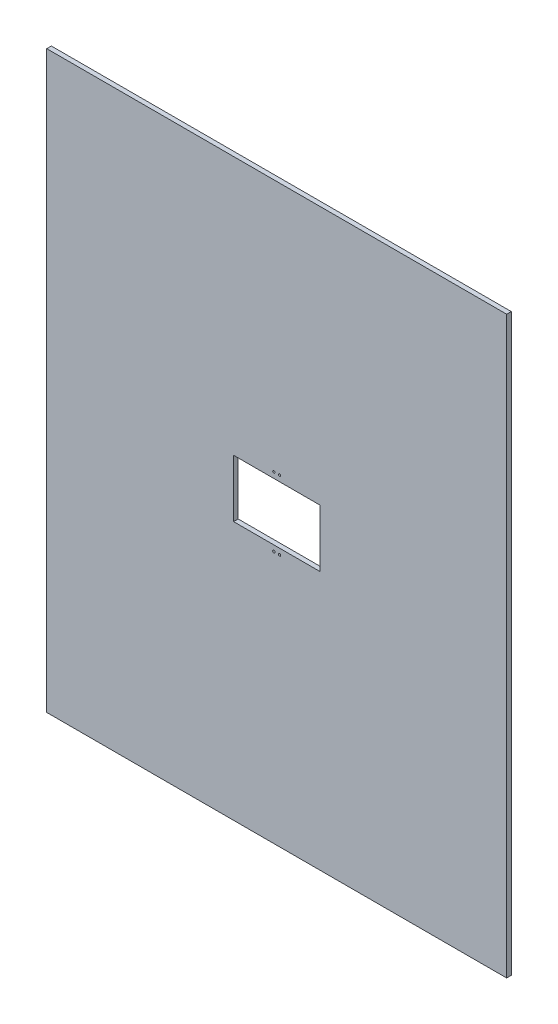
SolidWorks part; units mm, degrees
ref_plane "Front Plane" through (0, 0, 0) normal (0, 0, 1) x (1, 0, 0)
ref_plane "Top Plane" through (0, 0, 0) normal (0, 1, 0) x (1, 0, 0)
ref_plane "Right Plane" through (0, 0, 0) normal (1, 0, 0) x (0, 0, -1)
sketch "Sketch1" plane through (0, 0, 0) normal (0, 0, 1) x (1, 0, 0)
  line L1 (-400, 500) -> (400, 500)
  line L2 (-400, 500) -> (-400, -500)
  line L3 (-400, -500) -> (400, -500)
  line L4 (400, 500) -> (400, -500)
  line L5 (-400, 500) -> (400, -500) construction
  line L6 (-400, -500) -> (400, 500) construction
  point P0 (0, 0)
  dimension "D1" = 800
  dimension "D2" = 1000
extrude "Boss-Extrude1" add sketch "Sketch1" along normal blind 8
sketch "Sketch4" plane through (0, 0, 0) normal (0, 0, -1) x (-1, 0, 0)
  circle A0 centre (0, 0) radius 15 construction
  circle A1 centre (0, 15) radius 1.5
  circle A2 centre (15, 0) radius 1.5
  circle A3 centre (0, -15) radius 1.5
  circle A4 centre (-15, 0) radius 1.5
  point P14 (0, 0)
  dimension "D1" = 30
  dimension "D2" = 4
extrude "Cut-Extrude3" cut sketch "Sketch4" against normal blind 10
sketch "Sketch5" plane through (0, 0, 0) normal (0, 0, -1) x (-1, 0, 0)
  line L1 (-75, 50) -> (75, 50)
  line L2 (-75, 50) -> (-75, -50)
  line L3 (-75, -50) -> (75, -50)
  line L4 (75, 50) -> (75, -50)
  line L5 (-75, 50) -> (75, -50) construction
  line L6 (-75, -50) -> (75, 50) construction
  point P0 (0, 0)
  dimension "D1" = 150
  dimension "D2" = 100
extrude "Cut-Extrude4" cut sketch "Sketch5" against normal blind 10
sketch "Sketch6" plane through (0, 0, 0) normal (0, 0, -1) x (-1, 0, 0)
  line L0 (-195.8309, 0) -> (243.0877, 0) construction
  line L1 (0, 50) -> (0, -50) construction
  line L2 (-75, -50) -> (75, -50) construction
  circle A0 centre (-5, -60) radius 2
  circle A1 centre (5, -60) radius 2
  circle A2 centre (5, 60) radius 2
  circle A3 centre (-5, 60) radius 2
  point P13 (0, 0)
  point P17 (0, -50)
  dimension "D1" = 4
  dimension "D2" = 4
  dimension "D3" = 10
  dimension "D4" = 10
  dimension "D5" = 5
  dimension "D6" = 5
extrude "Cut-Extrude5" cut sketch "Sketch6" against normal blind 20
